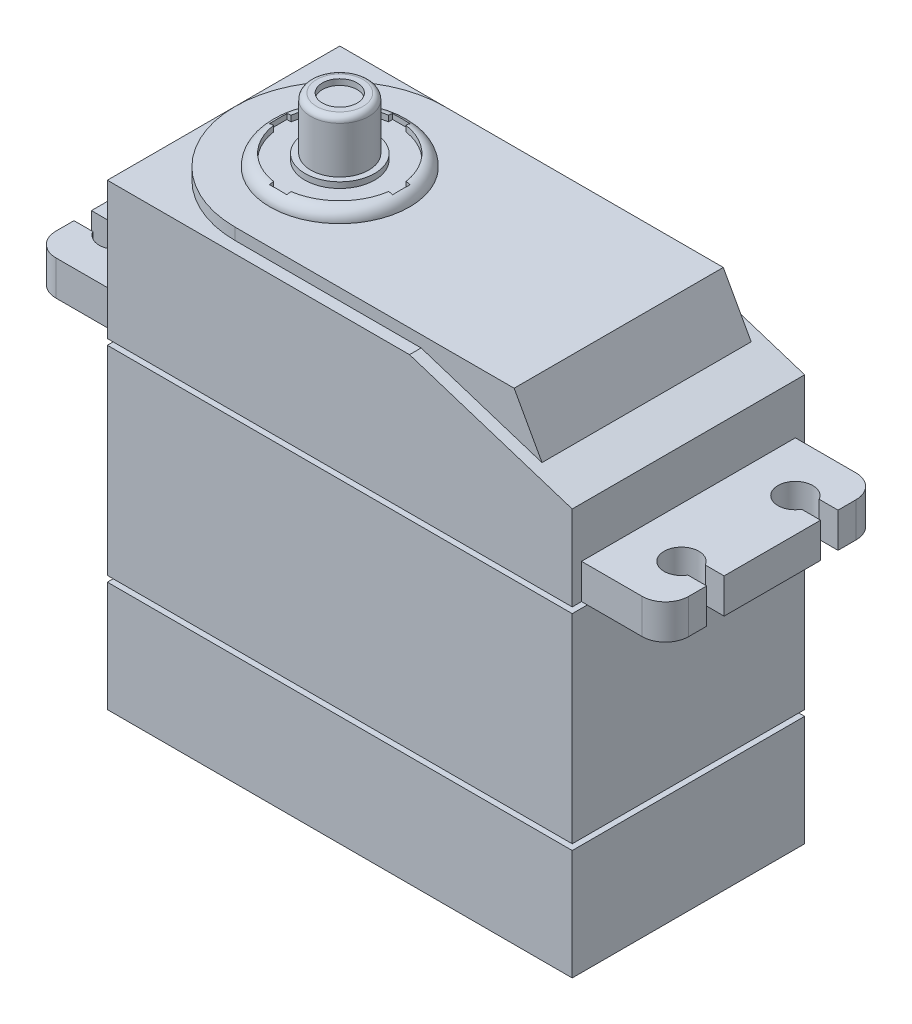
SolidWorks part; units mm, degrees
ref_plane "前视基准面" through (0, 0, 0) normal (0, 0, 1) x (1, 0, 0)
ref_plane "上视基准面" through (0, 0, 0) normal (0, 1, 0) x (1, 0, 0)
ref_plane "右视基准面" through (0, 0, 0) normal (1, 0, 0) x (0, 0, -1)
other "Configuration Table"
sketch "草图1" plane through (0, 0, 0) normal (0, 1, 0) x (1, 0, 0)
  line L1 (-20, -10) -> (20, -10)
  line L2 (-20, -10) -> (-20, 10)
  line L3 (-20, 10) -> (20, 10)
  line L4 (20, -10) -> (20, 10)
  line L5 (-20, -10) -> (20, 10) construction
  line L6 (-20, 10) -> (20, -10) construction
  point P0 (0, 0)
  dimension "D1" = 40
  dimension "D2" = 20
extrude "凸台-拉伸1" add sketch "草图1" along normal blind 40.45
ref_plane "基准面1" through (0, 27.65, 0) normal (0, -1, 0) x (-1, 0, 0)
sketch "草图2" plane through (0, 27.65, 0) normal (0, -1, 0) x (-1, 0, 0)
  line L0 (-29.8165, 0) -> (29.0273, 0) construction
  line L1 (20, 9.2) -> (27.22, 9.2)
  line L2 (27.22, 9.2) -> (27.22, 5.65)
  line L3 (27.22, -9.2) -> (20, -9.2)
  line L4 (-20, 10) -> (-20, -10)
  line L5 (-20, -10) -> (20, -10)
  line L6 (20, -10) -> (20, 10)
  line L7 (20, 10) -> (-20, 10)
  line L8 (-20, 9.2) -> (-20, -9.2)
  line L10 (20, -9.2) -> (20, 9.2)
  line L12 (-20, 9.2) -> (-27.22, 9.2)
  line L13 (-27.22, 9.2) -> (-27.22, 5.65)
  line L14 (-27.22, -9.2) -> (-20, -9.2)
  line L15 (0, 30.8227) -> (0, -21.1766) construction
  line L16 (-20, 10) -> (20, 10) construction
  line L17 (20, -10) -> (-20, -10) construction
  line L18 (24.3, 14.7246) -> (24.3, -13.2971) construction
  line L19 (27.22, 5.65) -> (25.599, 5.65)
  line L20 (27.22, 4.15) -> (25.599, 4.15)
  line L21 (27.22, 4.15) -> (27.22, -4.15)
  line L22 (27.22, -4.15) -> (25.599, -4.15)
  line L23 (27.22, -5.65) -> (25.599, -5.65)
  line L24 (-27.22, 5.65) -> (-25.599, 5.65)
  line L25 (-27.22, 4.15) -> (-25.599, 4.15)
  line L26 (-27.22, -5.65) -> (-25.599, -5.65)
  line L27 (-27.22, -4.15) -> (-25.599, -4.15)
  line L28 (27.22, -5.65) -> (27.22, -9.2)
  line L29 (-27.22, -5.65) -> (-27.22, -9.2)
  line L30 (-27.22, 4.15) -> (-27.22, -4.15)
  arc A0 (25.599, 5.65) -> (25.599, 4.15) centre (24.3, 4.9) ccw
  arc A1 (25.599, -5.65) -> (25.599, -4.15) centre (24.3, -4.9) cw
  arc A2 (-25.599, -5.65) -> (-25.599, -4.15) centre (-24.3, -4.9) ccw
  arc A3 (-25.599, 5.65) -> (-25.599, 4.15) centre (-24.3, 4.9) cw
  dimension "D6" = 3
  dimension "D2" = 0.8
  dimension "D4" = 0.8
  dimension "D5" = 27.22
  dimension "D7" = 24.3
  dimension "D8" = 9.8
  dimension "D9" = 1.5
  dimension "D10" = 0.75
  dimension "D1" = 0
extrude "凸台-拉伸2" add sketch "草图2" against normal blind 3
fillet "圆角1" radius 2 4 edges at (27.22, 29.15, -9.2) (27.22, 29.15, 9.2) (-27.22, 29.15, -9.2) (-27.22, 29.15, 9.2)
sketch "草图4" plane through (0, 27.65, 0) normal (0, -1, 0) x (-1, 0, 0)
  line L1 (-19.5, -9.5) -> (19.5, -9.5)
  line L2 (-19.5, -9.5) -> (-19.5, 9.5)
  line L3 (-19.5, 9.5) -> (19.5, 9.5)
  line L4 (-20, 10) -> (-20, -10)
  line L5 (-20, -10) -> (20, -10)
  line L6 (20, -10) -> (20, 10)
  line L7 (20, 10) -> (-20, 10)
  line L8 (-20, 10) -> (-20, -10)
  line L9 (-20, -10) -> (20, -10)
  line L10 (20, -10) -> (20, 10)
  line L11 (20, 10) -> (-20, 10)
  line L12 (19.5, -9.5) -> (19.5, 9.5)
  line L13 (-19.5, -9.5) -> (19.5, 9.5) construction
  line L14 (-19.5, 9.5) -> (19.5, -9.5) construction
  point P2 (0, 0)
  dimension "D2" = 0.5
  dimension "D3" = 0.5
  dimension "D1" = 0
extrude "切除-拉伸2" cut sketch "草图4" along normal blind 0.5
ref_plane "基准面2" through (0, 10, 0) normal (0, -1, 0) x (-1, 0, 0)
sketch "草图5" plane through (0, 10, 0) normal (0, -1, 0) x (-1, 0, 0)
  line L1 (-19.5, -9.5) -> (19.5, -9.5)
  line L2 (-19.5, -9.5) -> (-19.5, 9.5)
  line L3 (-19.5, 9.5) -> (19.5, 9.5)
  line L4 (-20, 10) -> (-20, -10)
  line L5 (-20, -10) -> (20, -10)
  line L6 (20, -10) -> (20, 10)
  line L7 (20, 10) -> (-20, 10)
  line L8 (-20, 10) -> (-20, -10)
  line L9 (-20, -10) -> (20, -10)
  line L10 (20, -10) -> (20, 10)
  line L11 (20, 10) -> (-20, 10)
  line L12 (19.5, -9.5) -> (19.5, 9.5)
  line L13 (-19.5, -9.5) -> (19.5, 9.5) construction
  line L14 (-19.5, 9.5) -> (19.5, -9.5) construction
  point P2 (0, 0)
  dimension "D2" = 0.5
  dimension "D3" = 0.5
  dimension "D1" = 0
extrude "切除-拉伸3" cut sketch "草图5" along normal blind 0.5
sketch "草图6" plane through (0, 40.45, 0) normal (0, 1, 0) x (1, 0, 0)
  line L0 (-33.1963, 0) -> (36.023, 0) construction
  circle A0 centre (-10, 0) radius 6
  dimension "D1" = 12
  dimension "D2" = 10
extrude "凸台-拉伸3" add sketch "草图6" along normal blind 1
fillet "圆角2" radius 1 1 edges at (-10, 41.45, 6)
sketch "草图7" plane through (0, 41.45, 0) normal (0, 1, 0) x (1, 0, 0)
  line L0 (-17.3226, 0) -> (1.4677, 0) construction
  line L1 (-10, 11.703) -> (-10, -14.1536) construction
  line L3 (-15.3, 0.75) -> (-15.3, -0.75)
  line L4 (-15.3, -0.75) -> (-14.9434, -0.75)
  line L6 (-9.25, 5.3) -> (-10.75, 5.3)
  line L7 (-10.75, 5.3) -> (-10.75, 4.9434)
  line L9 (-4.7, -0.75) -> (-4.7, 0.75)
  line L10 (-4.7, 0.75) -> (-5.0566, 0.75)
  line L12 (-10.75, -5.3) -> (-9.25, -5.3)
  line L13 (-9.25, -5.3) -> (-9.25, -4.9434)
  line L14 (-14.9434, 0.75) -> (-15.3, 0.75)
  line L16 (-5.0566, -0.75) -> (-4.7, -0.75)
  line L17 (-9.25, 4.9434) -> (-9.25, 5.3)
  line L18 (-10.75, -4.9434) -> (-10.75, -5.3)
  circle A0 centre (-10, 0) radius 2.5
  circle A1 centre (-10, 0) radius 3
  circle A2 centre (-10, 0) radius 5 construction
  arc A3 (-14.9434, -0.75) -> (-10.75, -4.9434) centre (-10, 0) ccw
  arc A4 (-10.75, 4.9434) -> (-14.9434, 0.75) centre (-10, 0) ccw
  arc A5 (-5.0566, 0.75) -> (-9.25, 4.9434) centre (-10, 0) ccw
  arc A6 (-9.25, -4.9434) -> (-5.0566, -0.75) centre (-10, 0) ccw
  point P32 (-10, 0)
  circle M23 centre (-10, 0) radius 5
  dimension "D1" = 5
  dimension "D2" = 6
  dimension "D3" = 5.3
  dimension "D4" = 1.5
  dimension "D5" = 0.75
  dimension "D7" = 5.3
  dimension "D6" = 4
extrude "切除-拉伸4" cut sketch "草图7" against normal blind 0.5 contours A1 M23 | L14 L3 L4 M23 | L18 L12 L13 M23 | L16 L9 L10 M23 | L17 L6 L7 M23 | A0 region at (-15.1401, 41.45, 0) region at (-13.4355, 41.45, -3.4355) region at (-10, 41.45, -5.1401) region at (-10, 41.45, 5.1401) region at (-4.8599, 41.45, 0) region at (-10, 41.45, 0)
sketch "草图8" plane through (0, 40.45, 0) normal (0, 1, 0) x (1, 0, 0)
  line L0 (-10, 9) -> (20, 9)
  line L1 (-10, -9) -> (20, -9)
  line L2 (20, 9) -> (20, 10)
  line L4 (20, -10) -> (20, 10)
  line L5 (20, 10) -> (-20, 10)
  line L6 (-20, 10) -> (-20, -10)
  line L7 (-20, -10) -> (20, -10)
  line L8 (20, -10) -> (20, -9)
  line L9 (20, 10) -> (-20, 10)
  line L10 (-20, 10) -> (-20, -10)
  line L11 (-20, -10) -> (20, -10)
  arc A0 (-10, 9) -> (-10, -9) centre (-10, 0) ccw
  dimension "D2" = 18
  dimension "D1" = 0
extrude "切除-拉伸6" cut sketch "草图8" against normal blind 1
sketch "草图9" plane through (0, 0, 10) normal (0, 0, 1) x (1, 0, 0)
  line L0 (6, 39.45) -> (20, 34.95)
  line L1 (-20, 39.45) -> (20, 39.45) construction
  line L2 (20, 39.45) -> (20, 27.65) construction
  line L3 (20, 34.95) -> (20, 39.45)
  line L4 (20, 39.45) -> (6, 39.45)
  dimension "D1" = 4.5
  dimension "D2" = 14
extrude "切除-拉伸7" cut sketch "草图9" against normal blind 1 contours L4 L0 L3
mirror "镜向1" about plane through (0, 0, 0) normal (0, 0, 1) of "切除-拉伸7"
sketch "草图10" plane through (0, 0, 9) normal (0, 0, 1) x (1, 0, 0)
  line L0 (14, 40.45) -> (16.4, 36.1071)
  line L1 (20, 40.45) -> (-10, 40.45) construction
  line L2 (6, 39.45) -> (20, 34.95) construction
  line L3 (14, 40.45) -> (20, 40.45)
  line L4 (20, 40.45) -> (20, 34.95)
  line L5 (20, 34.95) -> (16.4, 36.1071)
  dimension "D1" = 6
  dimension "D2" = 3.6
extrude "切除-拉伸8" cut sketch "草图10" against normal through all contours L5 L0 L3 L4
sketch "草图11" plane through (0, 40.95, 0) normal (0, 1, 0) x (1, 0, 0)
  circle A0 centre (-10, 0) radius 2.5
extrude "凸台-拉伸4" add sketch "草图11" along normal blind 5
sketch "草图12" plane through (0, 45.95, 0) normal (0, 1, 0) x (1, 0, 0)
  circle A0 centre (-10, 0) radius 1.5
  dimension "D1" = 3
extrude "切除-拉伸9" cut sketch "草图12" against normal blind 0.5
fillet "圆角3" radius 0.5 1 edges at (-10, 45.95, 2.5)
